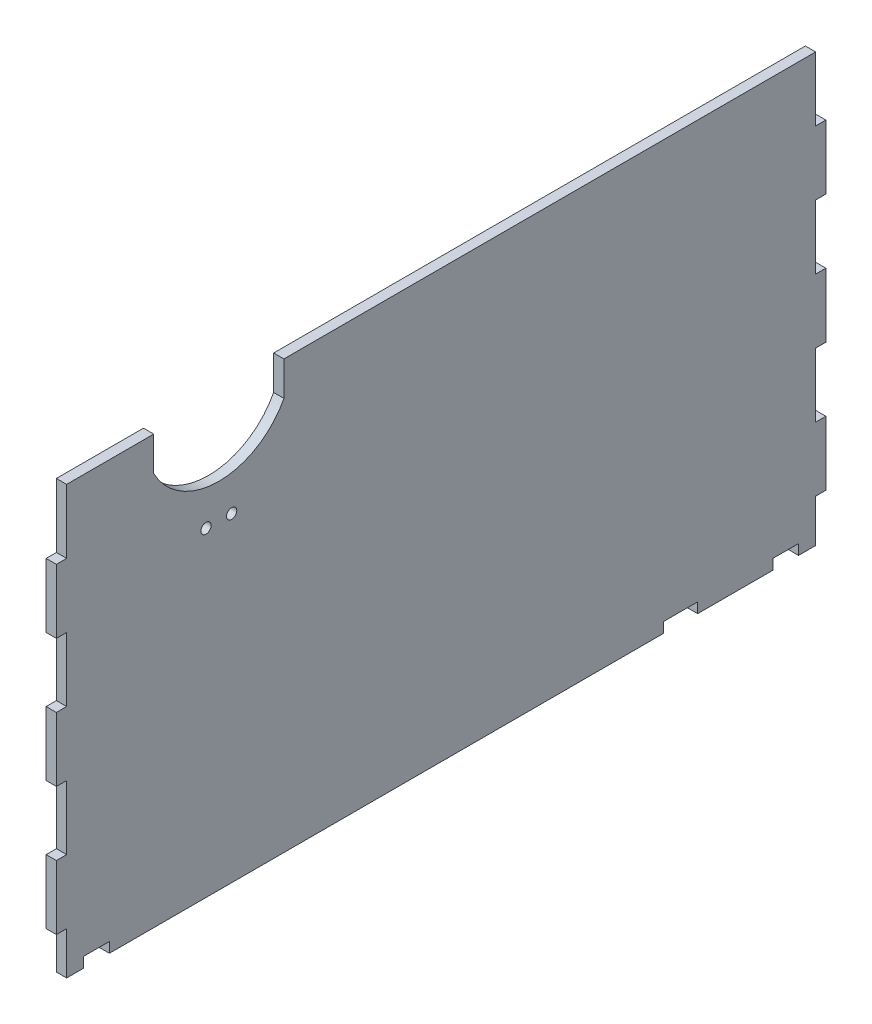
SolidWorks part; units mm, degrees
ref_plane "Front" through (0, 0, 0) normal (0, 0, 1) x (1, 0, 0)
ref_plane "Top" through (0, 0, 0) normal (0, 1, 0) x (1, 0, 0)
ref_plane "Right" through (0, 0, 0) normal (1, 0, 0) x (0, 0, -1)
sketch "Sketch1" plane through (0, 0, 0) normal (1, 0, 0) x (0, 0, -1)
  line L1 (0, 0) -> (-450, 0)
  line L2 (0, 0) -> (0, 250)
  line L3 (0, 250) -> (-450, 250)
  line L4 (-450, 0) -> (-450, 250)
  dimension "D1" = 450
  dimension "D2" = 250
extrude "Boss-Extrude1" add sketch "Sketch1" along normal blind 6
sketch "Sketch2" plane through (6, 0, 0) normal (1, 0, 0) x (0, 0, -1)
  line L0 (-450, 250) -> (-450, 0) construction
  line L1 (-450, 250) -> (-444, 250)
  line L2 (-450, 250) -> (-450, 212.5)
  line L3 (-450, 212.5) -> (-444, 212.5)
  line L4 (-444, 250) -> (-444, 212.5)
  line L5 (0, 250) -> (-450, 250) construction
  dimension "D1" = 6
  dimension "D2" = 37.5
extrude "Cut-Extrude1" cut sketch "Sketch2" against normal through all
pattern_linear "LPattern1" count 4 spacing 75 along (0, -1, 0) count 2 spacing 444 along (0, 0, -1) of "Cut-Extrude1"
sketch "Sketch3" plane through (6, 0, 0) normal (1, 0, 0) x (0, 0, -1)
  line L0 (-444, 0) -> (-6, 0) construction
  line L1 (-434, 0) -> (-419, 0)
  line L2 (-434, 0) -> (-434, 6)
  line L3 (-434, 6) -> (-419, 6)
  line L4 (-419, 0) -> (-419, 6)
  line L6 (-444, 62.5) -> (-444, 100) construction
  dimension "D1" = 10
  dimension "D2" = 15
  dimension "D3" = 6
extrude "Cut-Extrude2" cut sketch "Sketch3" against normal through all
pattern_linear "LPattern2" count 2 spacing 403 along (0, 0, -1) of "Cut-Extrude2"
sketch "Sketch4" plane through (6, 0, 0) normal (1, 0, 0) x (0, 0, -1)
  line L0 (-393.0657, 230) -> (-316.9343, 230) construction
  line L1 (-355, 250) -> (-355, 207) construction
  line L2 (-450, 212.5) -> (-450, 175) construction
  line L3 (-393.0657, 230) -> (-393.0657, 250)
  line L4 (-6, 250) -> (-444, 250) construction
  line L5 (-393.0657, 250) -> (-316.9343, 250)
  line L6 (-316.9343, 250) -> (-316.9343, 230)
  arc A0 (-393.0657, 230) -> (-316.9343, 230) centre (-355, 250) ccw
  circle A1 centre (-362.5, 187) radius 3
  circle A3 centre (-347.5, 187) radius 3
  dimension "D4" = 63
  dimension "D1" = 43
  dimension "D6" = 6
  dimension "D2" = 20
  dimension "D3" = 95
  dimension "D5" = 7.5
extrude "Cut-Extrude3" cut sketch "Sketch4" against normal blind 10
sketch "Sketch5" plane through (6, 0, 0) normal (1, 0, 0) x (0, 0, -1)
  line L0 (-419, 0) -> (-31, 0) construction
  line L1 (-75, 0) -> (-95, 0)
  line L2 (-75, 0) -> (-75, 6)
  line L3 (-75, 6) -> (-95, 6)
  line L4 (-95, 0) -> (-95, 6)
  line L5 (-16, 6) -> (-31, 6) construction
  line L6 (0, 25) -> (0, 62.5) construction
  dimension "D1" = 20
  dimension "D2" = 75
extrude "Cut-Extrude4" cut sketch "Sketch5" against normal through all
